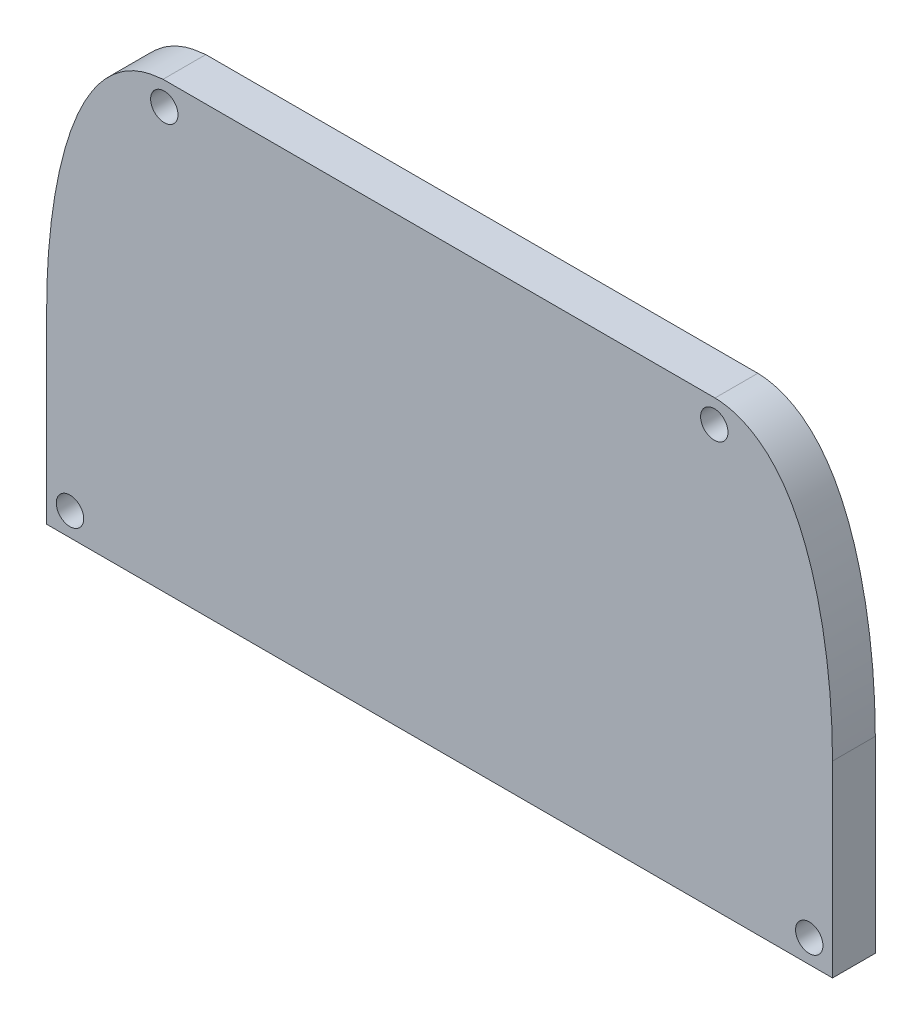
SolidWorks part; units mm, degrees
ref_plane "Front Plane" through (0, 0, 0) normal (0, 0, 1) x (1, 0, 0)
ref_plane "Top Plane" through (0, 0, 0) normal (0, 1, 0) x (1, 0, 0)
ref_plane "Right Plane" through (0, 0, 0) normal (1, 0, 0) x (0, 0, -1)
sketch "Sketch1" plane through (0, 0, 0) normal (0, 0, 1) x (1, 0, 0)
  line L0 (-29, 4.9329) -> (-29, 18.9593) construction
  line L1 (-29, 4.9329) -> (29, 4.9329) construction
  line L2 (29, 18.9593) -> (29, 4.9329) construction
  line L3 (-20.2196, 37.9329) -> (20.1267, 37.9329) construction
  line L4 (-29, 4.9329) -> (-29, 18.9593) construction
  line L5 (-29, 4.9329) -> (29, 4.9329) construction
  line L6 (29, 18.9593) -> (29, 4.9329) construction
  line L7 (-20.2196, 37.9329) -> (20.1267, 37.9329) construction
  line L8 (-20.2031, 37.6329) -> (20.1172, 37.6329)
  line L9 (28.7, 18.9573) -> (28.7, 5.2329)
  line L10 (-28.7, 5.2329) -> (28.7, 5.2329)
  line L11 (-28.7, 5.2329) -> (-28.7, 18.9574)
  spline S0 degree 2 poles (-31.9692, -1981.0344) (-29.7545, -9.9281) (-28.9753, 20.3809) (-28.956, 21.1325) (-28.9167, 21.8007) (-28.8758, 22.4979) (-28.8098, 23.2181) (-28.7437, 23.9403) (-28.6586, 24.6315) (-28.4799, 26.084) (-28.2121, 27.4233) (-27.9175, 28.8968) (-27.5367, 30.1575) (-27.0955, 31.6182) (-26.54, 32.811) (-26.2171, 33.5043) (-25.8726, 34.0804) (-25.4881, 34.7234) (-25.0615, 35.2597) (-24.6042, 35.8346) (-24.0818, 36.3005) (-23.8077, 36.5449) (-23.5308, 36.7481) (-23.2417, 36.9603) (-22.9324, 37.1389) (-22.6103, 37.3249) (-22.2891, 37.4608) (-21.9641, 37.5983) (-21.6205, 37.6954) (-21.3002, 37.7859) (-20.9286, 37.8453) (-20.7579, 37.8725) (-20.5753, 37.8935) (-17.3507, 38.2646) (1967.8393, 255.5742) knots -3.936313 -3.936313 -3.936313 0.0625 0.0625 0.125 0.125 0.1875 0.1875 0.25 0.25 0.375 0.375 0.5 0.5 0.625 0.625 0.6875 0.6875 0.75 0.75 0.8125 0.8125 0.84375 0.84375 0.875 0.875 0.90625 0.90625 0.9375 0.9375 0.96875 0.96875 0.984375 0.984375 2.300936 2.300936 2.300936 only from (-29, 18.9593) to (-20.2196, 37.9329) construction
  spline S1 degree 2 poles (-1977.1742, 141.4907) (9.4885, 38.8169) (20.4852, 37.9083) (20.6703, 37.893) (20.8404, 37.8684) (21.2069, 37.8154) (21.537, 37.7239) (21.7643, 37.6608) (21.9906, 37.5773) (22.4388, 37.4119) (22.8602, 37.1763) (23.1749, 37.0004) (23.4635, 36.7958) (23.748, 36.5941) (24.0261, 36.3514) (24.5413, 35.902) (25.0135, 35.3191) (25.3594, 34.8921) (25.6787, 34.3934) (25.9078, 34.0356) (26.1167, 33.6528) (26.3118, 33.295) (26.5032, 32.8894) (27.0665, 31.6959) (27.5124, 30.2375) (27.9021, 28.9627) (28.2027, 27.4702) (28.4749, 26.1185) (28.6558, 24.6546) (28.7415, 23.9614) (28.8083, 23.2347) (28.8748, 22.5113) (28.9161, 21.8119) (28.9558, 21.1393) (28.9752, 20.3865) (29.7594, -10.0157) (31.6782, -1981.0151) knots -1.71869 -1.71869 -1.71869 0.015625 0.015625 0.03125 0.03125 0.0625 0.0625 0.083333 0.083333 0.125 0.125 0.15625 0.15625 0.1875 0.1875 0.25 0.25 0.3 0.3 0.3375 0.3375 0.375 0.375 0.5 0.5 0.625 0.625 0.75 0.75 0.8125 0.8125 0.875 0.875 0.9375 0.9375 4.930379 4.930379 4.930379 only from (20.1267, 37.9329) to (29, 18.9593) construction
  spline S2 degree 2 poles (-29, 18.9593) (-28.9875, 19.9072) (-28.9753, 20.3809) (-28.956, 21.1325) (-28.9167, 21.8007) (-28.8758, 22.4979) (-28.8098, 23.2181) (-28.7437, 23.9403) (-28.6586, 24.6315) (-28.4799, 26.084) (-28.2121, 27.4233) (-27.9175, 28.8968) (-27.5367, 30.1575) (-27.0955, 31.6182) (-26.54, 32.811) (-26.2171, 33.5043) (-25.8726, 34.0804) (-25.4881, 34.7234) (-25.0615, 35.2597) (-24.6042, 35.8346) (-24.0818, 36.3005) (-23.8077, 36.5449) (-23.5308, 36.7481) (-23.2417, 36.9603) (-22.9324, 37.1389) (-22.6103, 37.3249) (-22.2891, 37.4608) (-21.9641, 37.5983) (-21.6205, 37.6954) (-21.3002, 37.7859) (-20.9286, 37.8453) (-20.7579, 37.8725) (-20.5753, 37.8935) (-20.537, 37.8979) (-20.2196, 37.9329) knots 0 0 0 0.0625 0.0625 0.125 0.125 0.1875 0.1875 0.25 0.25 0.375 0.375 0.5 0.5 0.625 0.625 0.6875 0.6875 0.75 0.75 0.8125 0.8125 0.84375 0.84375 0.875 0.875 0.90625 0.90625 0.9375 0.9375 0.96875 0.96875 0.984375 0.984375 1 1 1 construction
  spline S3 degree 2 poles (20.1267, 37.9329) (20.3861, 37.9165) (20.4852, 37.9083) (20.6703, 37.893) (20.8404, 37.8684) (21.2069, 37.8154) (21.537, 37.7239) (21.7643, 37.6608) (21.9906, 37.5773) (22.4388, 37.4119) (22.8602, 37.1763) (23.1749, 37.0004) (23.4635, 36.7958) (23.748, 36.5941) (24.0261, 36.3514) (24.5413, 35.902) (25.0135, 35.3191) (25.3594, 34.8921) (25.6787, 34.3934) (25.9078, 34.0356) (26.1167, 33.6528) (26.3118, 33.295) (26.5032, 32.8894) (27.0665, 31.6959) (27.5124, 30.2375) (27.9021, 28.9627) (28.2027, 27.4702) (28.4749, 26.1185) (28.6558, 24.6546) (28.7415, 23.9614) (28.8083, 23.2347) (28.8748, 22.5113) (28.9161, 21.8119) (28.9558, 21.1393) (28.9752, 20.3865) (28.9874, 19.9106) (29, 18.9593) knots 0 0 0 0.015625 0.015625 0.03125 0.03125 0.0625 0.0625 0.083333 0.083333 0.125 0.125 0.15625 0.15625 0.1875 0.1875 0.25 0.25 0.3 0.3 0.3375 0.3375 0.375 0.375 0.5 0.5 0.625 0.625 0.75 0.75 0.8125 0.8125 0.875 0.875 0.9375 0.9375 1 1 1 construction
  spline S4 degree 1 poles (-28.7, 18.9574) (-20.2031, 37.6329) knots 0 0 1 1 construction
  spline S5 degree 1 poles (20.1172, 37.6329) (28.7, 18.9573) knots 0 0 1 1 construction
  spline S6 degree 2 poles (-28.7, 18.9574) (-28.6922, 19.5495) (-28.6822, 20.0751) (-28.6783, 20.2529) (-28.6757, 20.3629) (-28.6703, 20.5617) (-28.6632, 20.7874) (-28.6482, 21.1914) (-28.6106, 21.9482) (-28.5163, 23.1936) (-28.3675, 24.5902) (-28.1922, 25.8371) (-28.0466, 26.695) (-27.9221, 27.3529) (-27.7681, 28.0843) (-27.607, 28.7711) (-27.4336, 29.4378) (-27.2573, 30.0537) (-27.0269, 30.7785) (-26.7898, 31.4448) (-26.536, 32.0848) (-26.2795, 32.6687) (-25.9472, 33.3431) (-25.627, 33.9166) (-25.2342, 34.5315) (-24.8389, 35.0682) (-24.3769, 35.6049) (-23.7716, 36.1955) (-22.8103, 36.9097) (-21.7788, 37.3494) (-21.2366, 37.4847) (-20.6299, 37.5979) (-20.2031, 37.6329) knots 0.000065 0.000065 0.000065 0.039109 0.050823 0.058631 0.06644 0.074249 0.085962 0.109389 0.156242 0.218712 0.281182 0.328035 0.35927 0.390506 0.421741 0.452976 0.484211 0.515446 0.546682 0.577917 0.609152 0.640387 0.671623 0.702858 0.734093 0.765328 0.796563 0.843416 0.905887 0.944931 0.960548 0.999592 0.999592 0.999592
  spline S7 degree 2 poles (20.1172, 37.6329) (21.1568, 37.6062) (22.7359, 36.9465) (23.72, 36.2416) (24.3173, 35.6683) (24.7922, 35.1263) (25.1938, 34.5895) (25.5802, 33.9943) (25.8807, 33.4639) (26.076, 33.0849) (26.2758, 32.6728) (26.5028, 32.1634) (26.76, 31.5234) (27, 30.8576) (27.2326, 30.1354) (27.4136, 29.5107) (27.5908, 28.8363) (27.7554, 28.1411) (27.9128, 27.3997) (28.0391, 26.7364) (28.187, 25.8709) (28.3648, 24.6129) (28.5147, 23.2105) (28.6098, 21.9608) (28.6478, 21.1995) (28.663, 20.7941) (28.6701, 20.5678) (28.6756, 20.3688) (28.6782, 20.258) (28.6822, 20.0795) (28.6921, 19.5518) (28.7, 18.9573) knots 0.000288 0.000288 0.000288 0.094005 0.156483 0.203341 0.23458 0.265819 0.297058 0.328297 0.351726 0.367346 0.390775 0.422014 0.453253 0.484492 0.515731 0.54697 0.578209 0.609448 0.640687 0.671926 0.718784 0.781262 0.84374 0.890599 0.914028 0.925742 0.933552 0.941362 0.949172 0.960886 0.999935 0.999935 0.999935
  dimension "D1" = 0.3
extrude "Boss-Extrude1" add sketch "Sketch1" along normal blind 3.125
sketch "Sketch2" plane through (0, 0, 3.125) normal (0, 0, 1) x (1, 0, 0)
  line L4 (-28.7, 18.9574) -> (-28.7, 5.2329)
  line L5 (-28.7, 5.2329) -> (28.7, 5.2329)
  line L6 (28.7, 5.2329) -> (28.7, 18.9573)
  line L7 (20.1172, 37.6329) -> (-20.2031, 37.6329)
  line L8 (-28.7, 18.9574) -> (-28.7, 5.2329)
  line L9 (-28.7, 5.2329) -> (28.7, 5.2329)
  line L10 (28.7, 5.2329) -> (28.7, 18.9573)
  line L11 (20.1172, 37.6329) -> (-20.2031, 37.6329)
  circle A0 centre (-27, 6.9329) radius 0.8 construction
  circle A1 centre (27, 6.9329) radius 0.8 construction
  circle A2 centre (20.0628, 35.9329) radius 0.8 construction
  circle A3 centre (-20.1097, 35.9329) radius 0.8 construction
  circle A4 centre (-27, 6.9329) radius 0.8 construction
  circle A5 centre (27, 6.9329) radius 0.8 construction
  circle A6 centre (20.0628, 35.9329) radius 0.8 construction
  circle A7 centre (-20.1097, 35.9329) radius 0.8 construction
  circle A8 centre (-27, 6.9329) radius 1
  circle A9 centre (-20.1097, 35.9329) radius 1
  circle A10 centre (20.0628, 35.9329) radius 1
  circle A11 centre (27, 6.9329) radius 1
  spline S2 degree 2 poles (-126.3941, -1958.189) (70.0796, 54.5226) (-21.2366, 37.4847) (-21.7788, 37.3494) (-22.8103, 36.9097) (-23.7716, 36.1955) (-24.3769, 35.6049) (-24.8389, 35.0682) (-25.2342, 34.5315) (-25.627, 33.9166) (-25.9472, 33.3431) (-26.2795, 32.6687) (-26.536, 32.0848) (-26.7898, 31.4448) (-27.0269, 30.7785) (-27.2573, 30.0537) (-27.4336, 29.4378) (-27.607, 28.7711) (-27.7681, 28.0843) (-27.9221, 27.3529) (-28.0466, 26.695) (-28.1922, 25.8371) (-28.3675, 24.5902) (-28.5163, 23.1936) (-28.6106, 21.9482) (-28.6482, 21.1914) (-28.6632, 20.7874) (-28.6703, 20.5617) (-28.6757, 20.3629) (-28.6783, 20.2529) (-28.6822, 20.0751) (-29.4557, -20.8947) (-32.4204, -1981.0017) knots -8.173358 -8.173358 -8.173358 0.039109 0.054727 0.093771 0.156242 0.203094 0.23433 0.265565 0.2968 0.328035 0.35927 0.390506 0.421741 0.452976 0.484211 0.515446 0.546682 0.577917 0.609152 0.640387 0.671623 0.718475 0.780946 0.843416 0.890269 0.913695 0.925409 0.933217 0.941026 0.948835 0.960548 4.905968 4.905968 4.905968 only from (-20.2031, 37.6329) to (-28.7, 18.9574)
  spline S3 degree 2 poles (32.1314, -1980.9949) (29.4589, -20.9988) (28.6822, 20.0795) (28.6782, 20.258) (28.6756, 20.3688) (28.6701, 20.5678) (28.663, 20.7941) (28.6478, 21.1995) (28.6098, 21.9608) (28.5147, 23.2105) (28.3648, 24.6129) (28.187, 25.8709) (28.0391, 26.7364) (27.9128, 27.3997) (27.7554, 28.1411) (27.5908, 28.8363) (27.4136, 29.5107) (27.2326, 30.1354) (27, 30.8576) (26.76, 31.5234) (26.5028, 32.1634) (26.2758, 32.6728) (26.076, 33.0849) (25.8807, 33.4639) (25.5802, 33.9943) (25.1938, 34.5895) (24.7922, 35.1263) (24.3173, 35.6683) (23.72, 36.2416) (22.7359, 36.9465) (-46.8807, 66.0263) (-604.2101, -1861.473) knots -3.900434 -3.900434 -3.900434 0.039337 0.051051 0.058861 0.066671 0.074481 0.086195 0.109624 0.156483 0.218961 0.281439 0.328297 0.359536 0.390775 0.422014 0.453253 0.484492 0.515731 0.54697 0.578209 0.609448 0.632877 0.648497 0.671926 0.703165 0.734404 0.765643 0.796882 0.84374 0.906218 7.729625 7.729625 7.729625 only from (28.7, 18.9573) to (20.1172, 37.6329)
  spline S4 degree 2 poles (-20.2031, 37.6329) (-20.6299, 37.5979) (-21.2366, 37.4847) (-21.7788, 37.3494) (-22.8103, 36.9097) (-23.7716, 36.1955) (-24.3769, 35.6049) (-24.8389, 35.0682) (-25.2342, 34.5315) (-25.627, 33.9166) (-25.9472, 33.3431) (-26.2795, 32.6687) (-26.536, 32.0848) (-26.7898, 31.4448) (-27.0269, 30.7785) (-27.2573, 30.0537) (-27.4336, 29.4378) (-27.607, 28.7711) (-27.7681, 28.0843) (-27.9221, 27.3529) (-28.0466, 26.695) (-28.1922, 25.8371) (-28.3675, 24.5902) (-28.5163, 23.1936) (-28.6106, 21.9482) (-28.6482, 21.1914) (-28.6632, 20.7874) (-28.6703, 20.5617) (-28.6757, 20.3629) (-28.6783, 20.2529) (-28.6822, 20.0751) (-28.6922, 19.5495) (-28.7, 18.9574) knots 0.000065 0.000065 0.000065 0.039109 0.054727 0.093771 0.156242 0.203094 0.23433 0.265565 0.2968 0.328035 0.35927 0.390506 0.421741 0.452976 0.484211 0.515446 0.546682 0.577917 0.609152 0.640387 0.671623 0.718475 0.780946 0.843416 0.890269 0.913695 0.925409 0.933217 0.941026 0.948835 0.960548 0.999592 0.999592 0.999592
  spline S5 degree 2 poles (28.7, 18.9573) (28.6921, 19.5518) (28.6822, 20.0795) (28.6782, 20.258) (28.6756, 20.3688) (28.6701, 20.5678) (28.663, 20.7941) (28.6478, 21.1995) (28.6098, 21.9608) (28.5147, 23.2105) (28.3648, 24.6129) (28.187, 25.8709) (28.0391, 26.7364) (27.9128, 27.3997) (27.7554, 28.1411) (27.5908, 28.8363) (27.4136, 29.5107) (27.2326, 30.1354) (27, 30.8576) (26.76, 31.5234) (26.5028, 32.1634) (26.2758, 32.6728) (26.076, 33.0849) (25.8807, 33.4639) (25.5802, 33.9943) (25.1938, 34.5895) (24.7922, 35.1263) (24.3173, 35.6683) (23.72, 36.2416) (22.7359, 36.9465) (21.1568, 37.6062) (20.1172, 37.6329) knots 0.000288 0.000288 0.000288 0.039337 0.051051 0.058861 0.066671 0.074481 0.086195 0.109624 0.156483 0.218961 0.281439 0.328297 0.359536 0.390775 0.422014 0.453253 0.484492 0.515731 0.54697 0.578209 0.609448 0.632877 0.648497 0.671926 0.703165 0.734404 0.765643 0.796882 0.84374 0.906218 0.999935 0.999935 0.999935
  point P26 (0, 0)
  point P27 (0, 0)
  dimension "D1" = 0
  dimension "D2" = 0.2
extrude "Cut-Extrude1" cut sketch "Sketch2" against normal through all contours A8 | A9 | A10 | A11 region at (-27, 6.9329, 3.125) region at (-20.1097, 35.9329, 3.125) region at (20.0628, 35.9329, 3.125) region at (27, 6.9329, 3.125)
